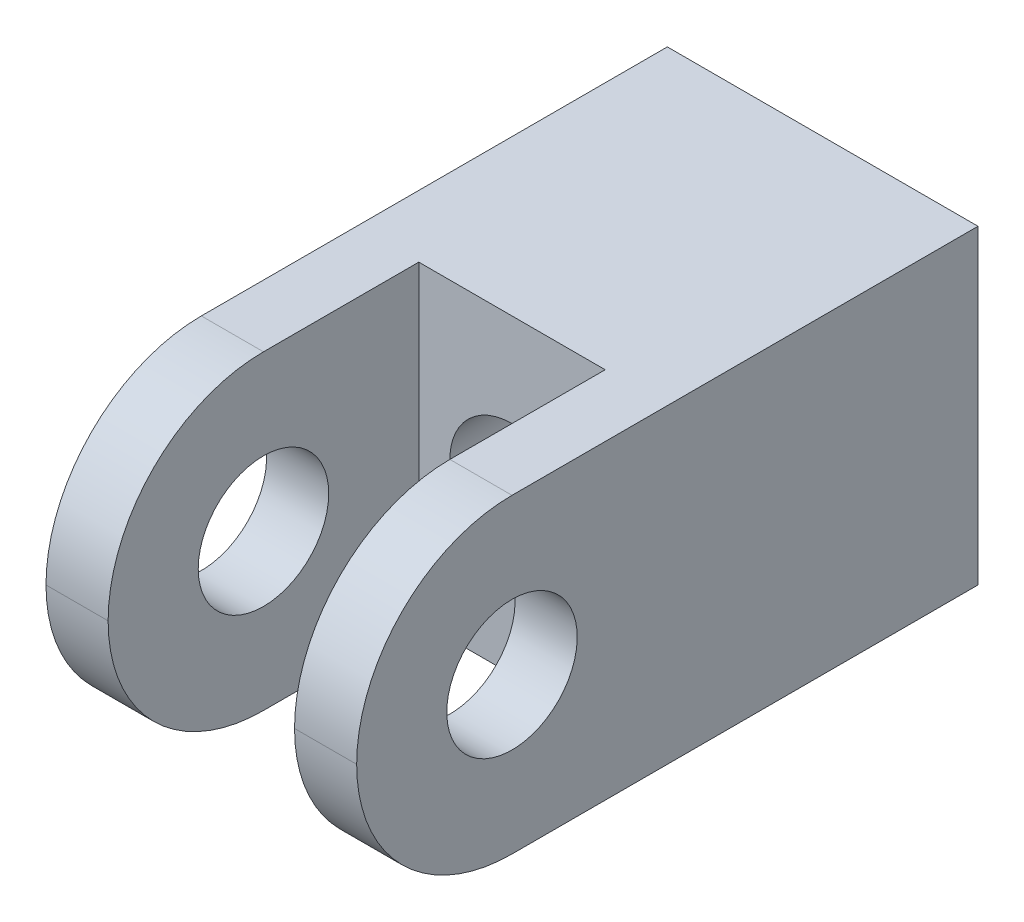
SolidWorks part; units mm, degrees
ref_plane "正面" through (0, 0, 0) normal (0, 0, 1) x (1, 0, 0)
ref_plane "平面" through (0, 0, 0) normal (0, 1, 0) x (1, 0, 0)
ref_plane "右側面" through (0, 0, 0) normal (1, 0, 0) x (0, 0, -1)
sketch "ｽｹｯﾁ1" plane through (0, 0, 0) normal (0, 0, 1) x (1, 0, 0)
  line L1 (-5, -5) -> (5, -5)
  line L2 (-5, -5) -> (-5, 5)
  line L3 (-5, 5) -> (5, 5)
  line L4 (5, -5) -> (5, 5)
  line L5 (-5, -5) -> (5, 5) construction
  line L6 (-5, 5) -> (5, -5) construction
  circle A0 centre (0, 0) radius 2
  point P0 (0, 0)
  dimension "D2" = 4
  dimension "D1" = 10
  dimension "D3" = 10
extrude "ﾎﾞｽ - 押し出し1" add sketch "ｽｹｯﾁ1" along normal blind 10
sketch "ｽｹｯﾁ2" plane through (0, 0, 10) normal (0, 0, 1) x (1, 0, 0)
  line L0 (-5, -5) -> (5, -5) construction
  line L1 (-5, 5) -> (-3, 5)
  line L2 (-5, 5) -> (-5, -5)
  line L3 (-5, -5) -> (-3, -5)
  line L4 (-3, 5) -> (-3, -5)
  line L5 (5, 5) -> (-5, 5) construction
  line L6 (3, 5) -> (5, 5)
  line L7 (3, 5) -> (3, -5)
  line L8 (3, -5) -> (5, -5)
  line L9 (5, 5) -> (5, -5)
  dimension "D1" = 2
  dimension "D2" = 2
extrude "ﾎﾞｽ - 押し出し2" add sketch "ｽｹｯﾁ2" along normal blind 10
sketch "ｽｹｯﾁ3" plane through (5, 0, 0) normal (1, 0, 0) x (0, 0, -1)
  line L0 (-20, -5) -> (-20, 5) construction
  circle A0 centre (-15, 0) radius 2.1
  dimension "D1" = 5
  dimension "D2" = 4.2
extrude "ｶｯﾄ - 押し出し1" cut sketch "ｽｹｯﾁ3" against normal blind 10
fillet "ﾌｨﾚｯﾄ1" radius 5 4 edges at (4, -5, 20) (4, 5, 20) (-4, 5, 20) (-4, -5, 20)
